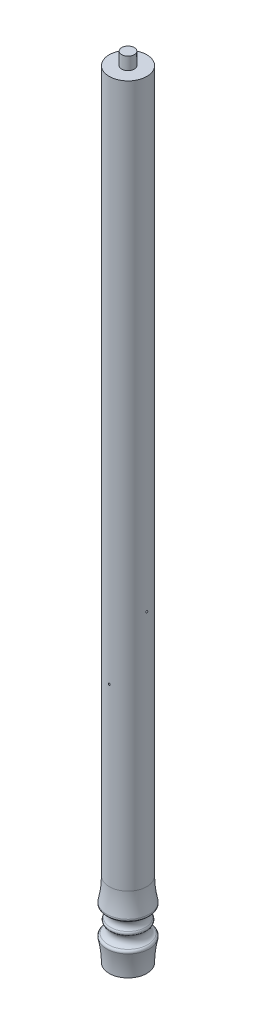
SolidWorks part; units mm, degrees
ref_plane "Front Plane" through (0, 0, 0) normal (0, 0, 1) x (1, 0, 0)
ref_plane "Top Plane" through (0, 0, 0) normal (0, 1, 0) x (1, 0, 0)
ref_plane "Right Plane" through (0, 0, 0) normal (1, 0, 0) x (0, 0, -1)
ref_plane "Plane3" through (0, 787.4, 0) normal (0, 1, 0) x (1, 0, 0)
ref_plane "Plane4" through (0, 800.1, 0) normal (0, 1, 0) x (1, 0, 0)
ref_plane "Plane5" through (0, 165.1, 0) normal (0, 1, 0) x (1, 0, 0)
ref_plane "Plane6" through (0, 203.2, 0) normal (0, 1, 0) x (1, 0, 0)
ref_plane "Plane7" through (0, 254, 0) normal (0, 1, 0) x (1, 0, 0)
ref_plane "Plane8" through (0, 25.4, 0) normal (0, 1, 0) x (1, 0, 0)
ref_plane "Plane9" through (0, 38.1, 0) normal (0, 1, 0) x (1, 0, 0)
ref_plane "Plane10" through (0, 50.8, 0) normal (0, 1, 0) x (1, 0, 0)
ref_plane "Plane11" through (0, 76.2, 0) normal (0, 1, 0) x (1, 0, 0)
ref_plane "Plane14" through (6.35, 0, 0) normal (1, 0, 0) x (0, 0, -1)
ref_plane "Plane15" through (15.875, 0, 0) normal (1, 0, 0) x (0, 0, -1)
ref_plane "Plane16" through (19.05, 0, 0) normal (1, 0, 0) x (0, 0, -1)
ref_plane "Plane17" through (22.225, 0, 0) normal (1, 0, 0) x (0, 0, -1)
sketch "center" plane through (0, 0, 0) normal (0, 0, 1) x (1, 0, 0)
  line L0 (0, 0) -> (0, 787.4)
  line L7 (154.1749, 787.4) -> (-154.1749, 787.4) construction
  line L13 (0, -76.5499) -> (0, 76.5499) construction
ref_axis "Axis1" through (0, -55, 0) along (0, 1, 0)
sketch "Sketch5" plane through (0, 25.4, 0) normal (0, 1, 0) x (1, 0, 0)
  line L0 (22.225, -76.5499) -> (22.225, 76.5499) construction
  circle A0 centre (0, 0) radius 22.225
ref_plane "Plane18" through (0, 31.75, 0) normal (0, 1, 0) x (1, 0, 0)
ref_plane "Plane19" through (0, 44.45, 0) normal (0, 1, 0) x (1, 0, 0)
sketch "Sketch6" plane through (0, 31.75, 0) normal (0, 1, 0) x (1, 0, 0)
  line L0 (15.875, -76.5499) -> (15.875, 76.5499) construction
  circle A0 centre (0, 0) radius 15.875
sketch "Sketch7" plane through (0, 38.1, 0) normal (0, 1, 0) x (1, 0, 0)
  circle A0 centre (0, 0) radius 18.9864
sketch "Sketch8" plane through (0, 44.45, 0) normal (0, 1, 0) x (1, 0, 0)
  circle A0 centre (0, 0) radius 15.875
sketch "Sketch9" plane through (0, 50.8, 0) normal (0, 1, 0) x (1, 0, 0)
  circle A0 centre (0, 0) radius 22.225
sketch "Sketch10" plane through (0, 76.2, 0) normal (0, 1, 0) x (1, 0, 0)
  circle A0 centre (0, 0) radius 18.9864
sketch "Sketch11" plane through (0, 0, 0) normal (0, 1, 0) x (1, 0, 0)
  circle A0 centre (0, 0) radius 18.9864
sketch "revolve sketch" plane through (0, 0, 0) normal (0, 0, 1) x (1, 0, 0)
  line L0 (0, 0) -> (19.05, 0)
  line L1 (18.9864, 0) -> (-18.9864, 0) construction
  line L2 (15.875, -76.5499) -> (15.875, 76.5499) construction
  line L3 (22.225, 25.4) -> (-22.225, 25.4) construction
  line L4 (22.225, -76.5499) -> (22.225, 76.5499) construction
  line L5 (154.1749, 25.4) -> (-154.1749, 25.4) construction
  line L6 (15.875, 31.75) -> (-15.875, 31.75) construction
  line L7 (154.1749, 31.75) -> (-154.1749, 31.75) construction
  line L8 (154.1749, 38.1) -> (-154.1749, 38.1) construction
  line L9 (15.875, 44.45) -> (-15.875, 44.45) construction
  line L10 (154.1749, 44.45) -> (-154.1749, 44.45) construction
  line L11 (22.225, 50.8) -> (-22.225, 50.8) construction
  line L12 (154.1749, 50.8) -> (-154.1749, 50.8) construction
  line L17 (19.05, -76.5499) -> (19.05, 76.5499) construction
  line L18 (154.1749, 0) -> (-154.1749, 0) construction
  line L19 (18.9864, 76.2) -> (-18.9864, 76.2) construction
  line L20 (154.1749, 76.2) -> (-154.1749, 76.2) construction
  line L21 (19.05, 76.2) -> (19.05, 787.4)
  line L22 (154.1749, 787.4) -> (-154.1749, 787.4) construction
  line L23 (19.05, 787.4) -> (6.35, 787.4)
  line L24 (6.35, -76.5499) -> (6.35, 76.5499) construction
  line L25 (6.35, 787.4) -> (6.35, 800.1)
  line L26 (152.7724, 800.1) -> (-152.7724, 800.1) construction
  line L27 (6.35, 800.1) -> (0, 800.1)
  line L28 (0, -76.5499) -> (0, 76.5499) construction
  line L29 (0, 800.1) -> (0, 0)
  arc A0 (19.05, 0) -> (21.6122, 22.8517) centre (122.2375, 0) cw
  arc A1 (15.875, 31.75) -> (20.018, 25.7959) centre (22.225, 31.75) ccw
  arc A2 (15.875, 31.75) -> (17.7809, 36.2857) centre (22.225, 31.75) cw
  arc A3 (17.7809, 39.9143) -> (15.875, 44.45) centre (22.225, 44.45) cw
  arc A4 (15.875, 44.45) -> (20.018, 50.4041) centre (22.225, 44.45) cw
  arc A5 (21.6122, 53.3483) -> (19.05, 76.2) centre (122.2375, 76.2) cw
  arc A6 (17.7809, 36.2857) -> (17.7809, 39.9143) centre (16.0033, 38.1) ccw
  arc A7 (21.6122, 22.8517) -> (20.018, 25.7959) centre (19.1352, 23.4142) ccw
  arc A8 (20.018, 50.4041) -> (21.6122, 53.3483) centre (19.1352, 52.7858) ccw
  point P49 (22.225, 38.1)
  point P52 (22.225, 25.4)
  point P55 (22.225, 50.8)
  point P60 (22.225, 25.4)
  point P62 (22.225, 50.8)
  dimension "D1" = 2.54
  dimension "D2" = 2.54
  dimension "D3" = 2.54
revolve "Revolve1" add sketch "revolve sketch" angle 360 about axis through (0, -55, 0) along (0, 1, 0)
ref_plane "Plane20" through (0, 317.5, 0) normal (0, 1, 0) x (1, 0, 0)
ref_axis "Axis2" through (162.1372, 317.5, 0) along (-1, 0, 0)
ref_axis "Axis3" through (0, 254, -88.99) along (0, 0, 1)
ref_axis "Axis4" through (0, 203.2, -88.99) along (0, 0, 1)
ref_axis "Axis5" through (0, 165.1, -88.99) along (0, 0, 1)
ref_plane "Plane21" through (0, 0, 6.35) normal (0, 0, 1) x (1, 0, 0)
ref_plane "Plane22" through (0, 0, 19.05) normal (0, 0, 1) x (1, 0, 0)
sketch "Sketch15" plane through (0, 0, 19.05) normal (0, 0, 1) x (1, 0, 0)
  line L0 (0, 0) -> (0, 787.4) construction
  line L1 (142.5044, 254) -> (-142.5044, 254) construction
  circle A0 centre (0, 254) radius 0.9922
  dimension "D1" = 1.9844
extrude "Cut-Extrude1" cut sketch "Sketch15" against normal up to surface (12.7 mm away) up to plane "Plane21"
sketch "Sketch16" plane through (19.05, 0, 0) normal (1, 0, 0) x (0, 0, -1)
  line L0 (142.5044, 317.5) -> (-142.5044, 317.5) construction
  line L1 (0, 0) -> (0, 787.4) construction
  circle A0 centre (0, 317.5) radius 0.9922
  dimension "D1" = 1.9844
extrude "Cut-Extrude2" cut sketch "Sketch16" against normal up to surface (12.7 mm away) contours A0 up to plane "Plane14"
ref_plane "Plane23" through (-19.05, 0, 0) normal (-1, 0, 0) x (0, 0, 1)
